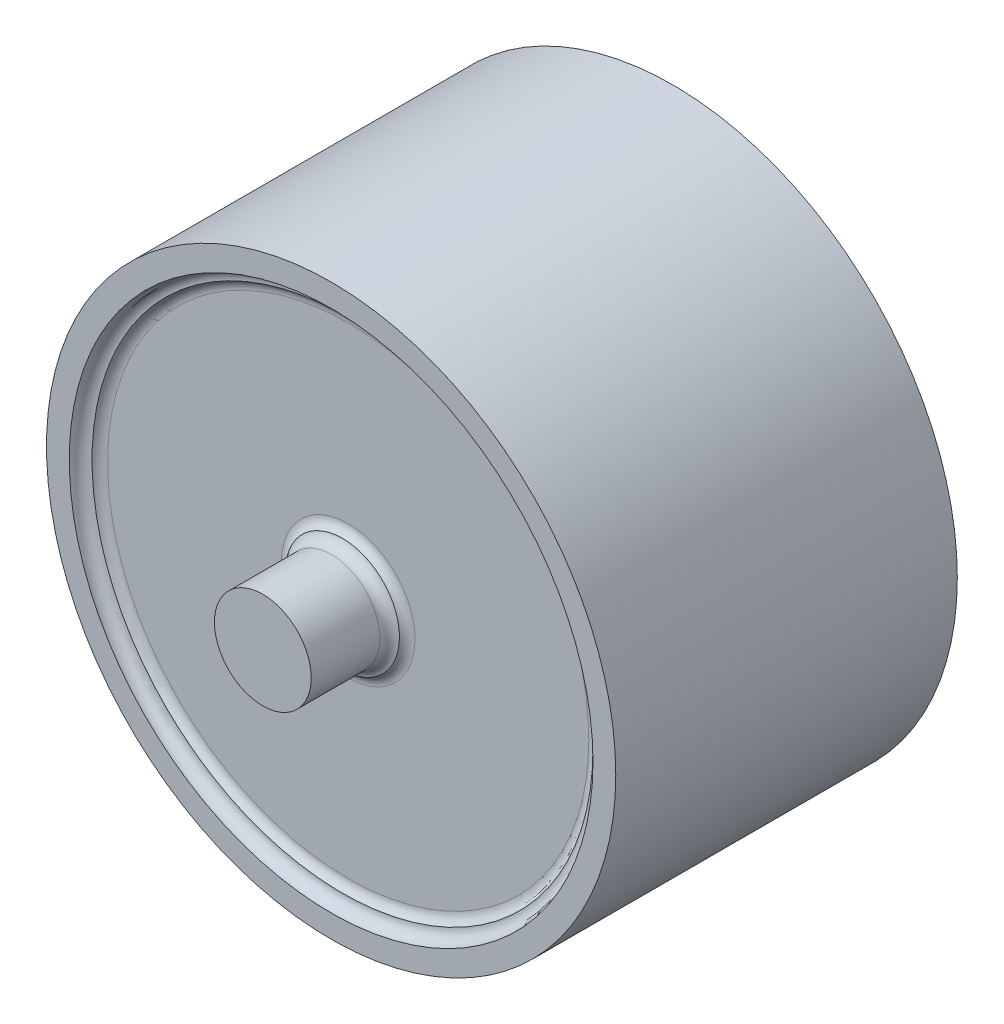
SolidWorks part; units mm, degrees
ref_plane "Front Plane" through (0, 0, 0) normal (0, 0, 1) x (1, 0, 0)
ref_plane "Top Plane" through (0, 0, 0) normal (0, 1, 0) x (1, 0, 0)
ref_plane "Right Plane" through (0, 0, 0) normal (1, 0, 0) x (0, 0, -1)
sketch "Sketch1" plane through (0, 0, 0) normal (0, 0, 1) x (1, 0, 0)
  circle A0 centre (0, 0) radius 250
  dimension "D1" = 500
extrude "Boss-Extrude1" add sketch "Sketch1" along normal blind 150 and the other way blind 150
sketch "Sketch2" plane through (0, 0, 150) normal (0, 0, 1) x (1, 0, 0)
  circle A0 centre (0, 0) radius 230
extrude "Cut-Extrude2" cut sketch "Sketch2" against normal blind 10 contours A0 region at (0, 0, 150)
sketch "Sketch3" plane through (0, 0, 140) normal (0, 0, 1) x (1, 0, 0)
  circle A0 centre (0, 0) radius 220
extrude "Cut-Extrude3" cut sketch "Sketch3" against normal blind 5
fillet "Fillet1" radius 10 1 edges at (230, 0, 140)
fillet "Fillet2" radius 10 1 edges at (220, 0, 135)
sketch "Sketch4" plane through (0, 0, 135) normal (0, 0, 1) x (1, 0, 0)
  circle A0 centre (0, 0) radius 50
extrude "Boss-Extrude2" add sketch "Sketch4" along normal blind 5
sketch "Sketch5" plane through (0, 0, 140) normal (0, 0, 1) x (1, 0, 0)
  circle A0 centre (0, 0) radius 42.5
  dimension "D1" = 85
extrude "Boss-Extrude3" add sketch "Sketch5" along normal blind 70 contours A0 region at (0, 0, 140)
sketch "Sketch6" plane through (0, 0, -150) normal (0, 0, -1) x (-1, 0, 0)
  circle A0 centre (0, 0) radius 50
extrude "Boss-Extrude4" add sketch "Sketch6" along normal blind 5
fillet "Fillet3" radius 10 2 edges at (42.5, 0, 140) (50, 0, 135)
scale "Scale1" scale about centroid uniform scaling yes scale factor 0.8
